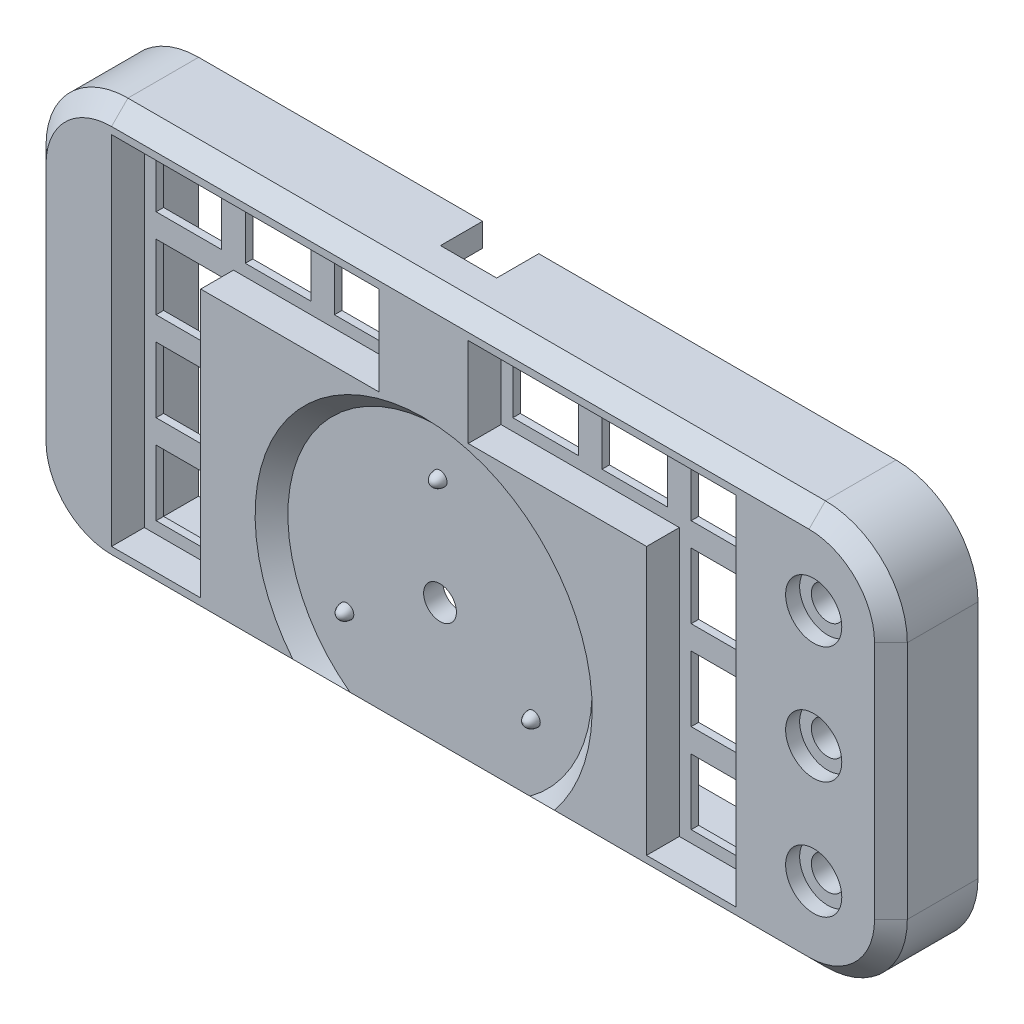
SolidWorks part; units mm, degrees
ref_plane "Alzado" through (0, 0, 0) normal (0, 0, 1) x (1, 0, 0)
ref_plane "Planta" through (0, 0, 0) normal (0, 1, 0) x (1, 0, 0)
ref_plane "Vista lateral" through (0, 0, 0) normal (1, 0, 0) x (0, 0, -1)
sketch "Croquis1" plane through (0, 0, 0) normal (0, 0, 1) x (1, 0, 0)
  line L0 (21.575, 59.675) -> (21.575, 73.675)
  line L1 (0, 0) -> (157.5, 0)
  line L2 (0, 0) -> (0, 76.2)
  line L3 (0, 76.2) -> (157.5, 76.2)
  line L4 (157.5, 0) -> (157.5, 76.2)
  line L5 (2.525, 59.675) -> (16.525, 59.675)
  line L6 (2.525, 59.675) -> (2.525, 73.675)
  line L7 (2.525, 73.675) -> (16.525, 73.675)
  line L8 (16.525, 59.675) -> (16.525, 73.675)
  line L9 (2.525, 59.675) -> (16.525, 73.675) construction
  line L10 (2.525, 73.675) -> (16.525, 59.675) construction
  line L11 (0, 76.2) -> (19.05, 76.2) construction
  line L12 (0, 76.2) -> (0, 57.15) construction
  line L13 (0, 57.15) -> (19.05, 57.15) construction
  line L14 (19.05, 76.2) -> (19.05, 57.15) construction
  line L15 (0, 76.2) -> (19.05, 57.15) construction
  line L16 (0, 57.15) -> (19.05, 76.2) construction
  line L17 (21.575, 59.675) -> (35.575, 59.675)
  line L18 (35.575, 59.675) -> (35.575, 73.675)
  line L19 (21.575, 73.675) -> (35.575, 73.675)
  line L20 (38.1, 76.2) -> (38.1, 57.15) construction
  line L21 (19.05, 57.15) -> (38.1, 57.15) construction
  line L22 (40.625, 59.675) -> (40.625, 73.675)
  line L23 (40.625, 59.675) -> (54.625, 59.675)
  line L24 (54.625, 59.675) -> (54.625, 73.675)
  line L25 (40.625, 73.675) -> (54.625, 73.675)
  line L26 (57.15, 76.2) -> (57.15, 57.15) construction
  line L27 (38.1, 57.15) -> (57.15, 57.15) construction
  line L28 (59.675, 59.675) -> (59.675, 73.675) construction
  line L29 (59.675, 59.675) -> (73.675, 59.675) construction
  line L30 (73.675, 59.675) -> (73.675, 73.675) construction
  line L31 (59.675, 73.675) -> (73.675, 73.675) construction
  line L32 (76.2, 76.2) -> (76.2, 57.15) construction
  line L33 (57.15, 57.15) -> (76.2, 57.15) construction
  line L34 (78.725, 59.675) -> (78.725, 73.675)
  line L35 (78.725, 59.675) -> (92.725, 59.675)
  line L36 (92.725, 59.675) -> (92.725, 73.675)
  line L37 (78.725, 73.675) -> (92.725, 73.675)
  line L38 (95.25, 76.2) -> (95.25, 57.15) construction
  line L39 (76.2, 57.15) -> (95.25, 57.15) construction
  line L40 (97.775, 59.675) -> (97.775, 73.675)
  line L41 (97.775, 59.675) -> (111.775, 59.675)
  line L42 (111.775, 59.675) -> (111.775, 73.675)
  line L43 (97.775, 73.675) -> (111.775, 73.675)
  line L44 (114.3, 76.2) -> (114.3, 57.15) construction
  line L45 (95.25, 57.15) -> (114.3, 57.15) construction
  line L46 (116.825, 59.675) -> (116.825, 73.675)
  line L47 (116.825, 59.675) -> (130.825, 59.675)
  line L48 (130.825, 59.675) -> (130.825, 73.675)
  line L49 (116.825, 73.675) -> (130.825, 73.675)
  line L50 (133.35, 76.2) -> (133.35, 57.15) construction
  line L51 (114.3, 57.15) -> (133.35, 57.15) construction
  line L52 (2.525, 59.675) -> (21.575, 59.675) construction
  line L53 (2.525, 40.625) -> (2.525, 54.625)
  line L54 (2.525, 40.625) -> (16.525, 40.625)
  line L55 (16.525, 40.625) -> (16.525, 54.625)
  line L56 (2.525, 54.625) -> (16.525, 54.625)
  line L57 (0, 38.1) -> (19.05, 38.1) construction
  line L58 (19.05, 57.15) -> (19.05, 38.1) construction
  line L59 (116.825, 40.625) -> (116.825, 54.625)
  line L60 (116.825, 54.625) -> (130.825, 54.625)
  line L61 (130.825, 40.625) -> (130.825, 54.625)
  line L62 (116.825, 40.625) -> (130.825, 40.625)
  line L63 (114.3, 57.15) -> (114.3, 38.1) construction
  line L64 (114.3, 38.1) -> (133.35, 38.1) construction
  line L65 (133.35, 57.15) -> (133.35, 38.1) construction
  line L66 (2.525, 21.575) -> (2.525, 35.575)
  line L67 (2.525, 21.575) -> (16.525, 21.575)
  line L68 (16.525, 21.575) -> (16.525, 35.575)
  line L69 (2.525, 35.575) -> (16.525, 35.575)
  line L70 (0, 19.05) -> (19.05, 19.05) construction
  line L71 (19.05, 38.1) -> (19.05, 19.05) construction
  line L72 (116.825, 21.575) -> (116.825, 35.575)
  line L73 (116.825, 35.575) -> (130.825, 35.575)
  line L74 (130.825, 21.575) -> (130.825, 35.575)
  line L75 (116.825, 21.575) -> (130.825, 21.575)
  line L76 (114.3, 38.1) -> (114.3, 19.05) construction
  line L77 (114.3, 19.05) -> (133.35, 19.05) construction
  line L78 (133.35, 38.1) -> (133.35, 19.05) construction
  line L79 (2.525, 2.525) -> (2.525, 16.525)
  line L80 (2.525, 2.525) -> (16.525, 2.525)
  line L81 (16.525, 2.525) -> (16.525, 16.525)
  line L82 (2.525, 16.525) -> (16.525, 16.525)
  line L83 (0, 0) -> (19.05, 0) construction
  line L84 (19.05, 19.05) -> (19.05, 0) construction
  line L85 (116.825, 2.525) -> (116.825, 16.525)
  line L86 (116.825, 16.525) -> (130.825, 16.525)
  line L87 (130.825, 2.525) -> (130.825, 16.525)
  line L88 (116.825, 2.525) -> (130.825, 2.525)
  line L89 (114.3, 19.05) -> (114.3, 0) construction
  line L90 (114.3, 0) -> (133.35, 0) construction
  line L91 (133.35, 19.05) -> (133.35, 0) construction
  line L92 (2.525, 59.675) -> (2.525, 40.625) construction
  line L104 (133.35, 38.1) -> (150, 38.1) construction
  line L105 (150, 63.1) -> (150, 38.1) construction
  line L121 (150, 38.1) -> (150, 13.1) construction
  line L122 (116.825, 40.625) -> (130.825, 54.625) construction
  circle A0 centre (150, 38.1) radius 3.5
  circle A1 centre (150, 63.1) radius 3.5
  circle A2 centre (150, 13.1) radius 3.5
  circle A3 centre (66.67, 21.2) radius 3.5
  point P5 (9.525, 66.675)
  point P10 (9.525, 66.675)
  point P15 (66.67, 21.2)
  point P119 (98, 28.2)
  dimension "D11" = 7
  dimension "D3" = 19.05
  dimension "D4" = 14
  dimension "D5" = 9.525
  dimension "D6" = 9.525
  dimension "D8" = 19.05
  dimension "D10" = 19.05
  dimension "D13" = 66.67
  dimension "D14" = 76.2
  dimension "D15" = 55
  dimension "D16" = 150
  dimension "D18" = 157.5
  dimension "D19" = 98
  dimension "D20" = 48
  dimension "D22" = 25
  dimension "D17" = 7.5
  dimension "D7" = 7
  dimension "D9" = 4
extrude "Saliente-Extruir1" add sketch "Croquis1" against normal blind 1.6
sketch "Croquis2" plane through (0, 0, 0) normal (0, 0, 1) x (1, 0, 0)
  line L0 (66.67, 21.2) -> (66.67, 83.1935) construction
  line L3 (0, -5) -> (66.67, -5)
  line L4 (166.5, 12.5) -> (166.5, 63.7)
  line L5 (149, 81.2) -> (0, 81.2)
  line L6 (-17.5, 63.7) -> (-17.5, 12.5)
  line L7 (150, 63.1) -> (150, 38.1) construction
  line L8 (0, 76.2) -> (157.5, 76.2) construction
  line L9 (-17.5, 38.1) -> (0, 38.1) construction
  line L10 (0, 0) -> (0, 76.2) construction
  line L11 (66.67, -5) -> (149, -5)
  line L13 (19.05, 0) -> (0, 0)
  line L14 (0, 0) -> (0, 76.2)
  line L15 (0, 76.2) -> (57.15, 76.2)
  line L16 (57.15, 76.2) -> (57.15, 57.15)
  line L17 (57.15, 57.15) -> (19.05, 57.15)
  line L18 (19.05, 57.15) -> (19.05, 0)
  line L19 (19.05, 0) -> (0, 0)
  line L20 (114.3, 0) -> (133.35, 0)
  line L21 (133.35, 0) -> (133.35, 76.2)
  line L22 (133.35, 76.2) -> (76.2, 76.2)
  line L23 (76.2, 76.2) -> (76.2, 57.15)
  line L24 (76.2, 57.15) -> (114.3, 57.15)
  line L25 (114.3, 57.15) -> (114.3, 0)
  arc A0 (166.5, 63.7) -> (149, 81.2) centre (149, 63.7) ccw
  arc A1 (149, -5) -> (166.5, 12.5) centre (149, 12.5) ccw
  arc A2 (0, -5) -> (-17.5, 12.5) centre (0, 12.5) cw
  arc A3 (0, 81.2) -> (-17.5, 63.7) centre (0, 63.7) ccw
  circle A5 centre (150, 13.1) radius 3.5 construction
  circle A6 centre (150, 63.1) radius 3.5 construction
  circle A7 centre (150, 38.1) radius 3.5 construction
  circle A8 centre (150, 13.1) radius 3.5
  circle A9 centre (150, 63.1) radius 3.5
  circle A10 centre (150, 38.1) radius 3.5
  circle A11 centre (66.67, 21.2) radius 3.5 construction
  circle A12 centre (66.67, 21.2) radius 3.5
  dimension "D3" = 17.5
  dimension "D1" = 16.5
  dimension "D2" = 5
extrude "Saliente-Extruir4" add sketch "Croquis2" against normal up to surface (1.6 mm away) and the other way blind 3.5 contours L11 A1 L4 A0 L5 A3 L6 A2 L3 A10 A9 A8 L25 L24 L23 L22 L21 L20 L17 L18 L13 L14 L15 L16 region at (76.8141, 34.4181, 0) up to face at (153.5, 13.1, -1.6)
sketch "Croquis3" plane through (0, 0, 3.5) normal (0, 0, 1) x (1, 0, 0)
  line L0 (76.2, 57.15) -> (114.3, 57.15) construction
  line L1 (76.2, 76.2) -> (76.2, 57.15) construction
  line L2 (133.35, 76.2) -> (76.2, 76.2) construction
  line L3 (133.35, 0) -> (133.35, 76.2) construction
  line L4 (114.3, 57.15) -> (114.3, 0) construction
  line L5 (114.3, 0) -> (133.35, 0) construction
  line L6 (19.05, 0) -> (0, 0) construction
  line L7 (19.05, 57.15) -> (19.05, 0) construction
  line L8 (57.15, 57.15) -> (19.05, 57.15) construction
  line L9 (57.15, 76.2) -> (57.15, 57.15) construction
  line L10 (0, 76.2) -> (57.15, 76.2) construction
  line L11 (0, 76.2) -> (0, 0) construction
  line L12 (76.2, 57.15) -> (114.3, 57.15)
  line L13 (76.2, 76.2) -> (76.2, 57.15)
  line L14 (133.35, 76.2) -> (76.2, 76.2)
  line L15 (133.35, 0) -> (133.35, 76.2)
  line L16 (114.3, 57.15) -> (114.3, 0)
  line L17 (114.3, 0) -> (133.35, 0)
  line L18 (19.05, 0) -> (0, 0)
  line L19 (19.05, 57.15) -> (19.05, 0)
  line L20 (57.15, 57.15) -> (19.05, 57.15)
  line L21 (57.15, 76.2) -> (57.15, 57.15)
  line L22 (0, 76.2) -> (57.15, 76.2)
  line L23 (0, 76.2) -> (0, 0)
  line L24 (85.9004, -5) -> (149, -5)
  line L28 (149, 81.2) -> (0, 81.2)
  line L29 (-17.5, 63.7) -> (-17.5, 12.5)
  line L30 (0, -5) -> (149, -5)
  line L31 (166.5, 12.5) -> (166.5, 63.7)
  line L32 (149, 81.2) -> (0, 81.2)
  line L33 (-17.5, 63.7) -> (-17.5, 12.5)
  line L34 (0, -5) -> (47.4396, -5)
  line L35 (166.5, 12.5) -> (166.5, 63.7)
  circle A0 centre (150, 63.1) radius 3.5 construction
  circle A1 centre (150, 38.1) radius 3.5 construction
  circle A2 centre (150, 13.1) radius 3.5 construction
  circle A3 centre (66.67, 21.2) radius 3.5 construction
  circle A4 centre (150, 63.1) radius 3.5
  circle A5 centre (150, 38.1) radius 3.5
  circle A6 centre (150, 13.1) radius 3.5
  circle A7 centre (66.67, 21.2) radius 3.5 construction
  arc A8 (85.9004, -5) -> (47.4396, -5) centre (66.67, 21.2) ccw
  arc A12 (0, 81.2) -> (-17.5, 63.7) centre (0, 63.7) ccw
  arc A13 (-17.5, 12.5) -> (0, -5) centre (0, 12.5) ccw
  arc A14 (149, -5) -> (166.5, 12.5) centre (149, 12.5) ccw
  arc A15 (166.5, 63.7) -> (149, 81.2) centre (149, 63.7) ccw
  arc A16 (0, 81.2) -> (-17.5, 63.7) centre (0, 63.7) ccw
  arc A17 (-17.5, 12.5) -> (0, -5) centre (0, 12.5) ccw
  arc A18 (149, -5) -> (166.5, 12.5) centre (149, 12.5) ccw
  arc A19 (166.5, 63.7) -> (149, 81.2) centre (149, 63.7) ccw
  dimension "D2" = 65
  dimension "D1" = 0
extrude "Saliente-Extruir5" add sketch "Croquis3" along normal blind 3.5
chamfer "Chaflán1" distance 3.5 angle 45 10 edges at (117.4502, -5, 7) (161.3744, 0.1256, 7) (166.5, 38.1, 7) (161.3744, 76.0744, 7) (74.5, 81.2, 7) (-12.3744, 76.0744, 7) (-17.5, 38.1, 7) (-12.3744, 0.1256, 7) (23.7198, -5, 7) (66.67, 53.7, 7)
sketch "Croquis4" plane through (0, 0, -1.6) normal (0, 0, -1) x (-1, 0, 0)
  line L1 (-157.25, 55.85) -> (-142.75, 55.85)
  line L2 (-157.25, 55.85) -> (-157.25, 70.35)
  line L3 (-157.25, 70.35) -> (-142.75, 70.35)
  line L4 (-142.75, 55.85) -> (-142.75, 70.35)
  line L5 (-157.25, 55.85) -> (-142.75, 70.35) construction
  line L6 (-157.25, 70.35) -> (-142.75, 55.85) construction
  line L7 (-157.25, 30.85) -> (-142.75, 30.85)
  line L8 (-157.25, 30.85) -> (-157.25, 45.35)
  line L9 (-157.25, 45.35) -> (-142.75, 45.35)
  line L10 (-142.75, 30.85) -> (-142.75, 45.35)
  line L11 (-157.25, 30.85) -> (-142.75, 45.35) construction
  line L12 (-157.25, 45.35) -> (-142.75, 30.85) construction
  line L13 (-157.25, 5.85) -> (-142.75, 5.85)
  line L14 (-157.25, 5.85) -> (-157.25, 20.35)
  line L15 (-157.25, 20.35) -> (-142.75, 20.35)
  line L16 (-142.75, 5.85) -> (-142.75, 20.35)
  line L17 (-157.25, 5.85) -> (-142.75, 20.35) construction
  line L18 (-157.25, 20.35) -> (-142.75, 5.85) construction
  line L19 (-73.92, 13.95) -> (-59.42, 13.95)
  line L20 (-73.92, 13.95) -> (-73.92, 28.45)
  line L21 (-73.92, 28.45) -> (-59.42, 28.45)
  line L22 (-59.42, 13.95) -> (-59.42, 28.45)
  line L23 (-73.92, 13.95) -> (-59.42, 28.45) construction
  line L24 (-73.92, 28.45) -> (-59.42, 13.95) construction
  point P0 (-150, 63.1)
  point P6 (-150, 38.1)
  point P12 (-150, 13.1)
  point P18 (-66.67, 21.2)
  dimension "D1" = 14.5
extrude "Cortar-Extruir1" cut sketch "Croquis4" against normal blind 1
sketch "Croquis5" plane through (0, 0, -1.6) normal (0, 0, -1) x (-1, 0, 0)
  line L0 (0, 76.2) -> (-149, 76.2)
  line L1 (-161.5, 63.7) -> (-161.5, 12.5)
  line L2 (-149, 0) -> (0, 0) construction
  line L4 (0, 81.2) -> (-149, 81.2)
  line L5 (-166.5, 63.7) -> (-166.5, 12.5)
  line L6 (-149, -5) -> (0, -5)
  line L7 (17.5, 12.5) -> (17.5, 63.7)
  line L8 (0, 81.2) -> (-149, 81.2)
  line L9 (-166.5, 63.7) -> (-166.5, 12.5)
  line L10 (-149, -5) -> (0, -5)
  line L11 (17.5, 12.5) -> (17.5, 63.7)
  line L12 (0, 0) -> (0, 76.2)
  line L13 (-149, 0) -> (0, 0)
  line L14 (0, 76.2) -> (-149, 76.2) construction
  line L16 (12.5, 12.5) -> (12.5, 63.7) construction
  arc A0 (-149, 76.2) -> (-161.5, 63.7) centre (-149, 63.7) ccw
  arc A1 (-161.5, 12.5) -> (-149, 0) centre (-149, 12.5) ccw
  arc A4 (-149, 81.2) -> (-166.5, 63.7) centre (-149, 63.7) ccw
  arc A5 (-166.5, 12.5) -> (-149, -5) centre (-149, 12.5) ccw
  arc A6 (0, -5) -> (17.5, 12.5) centre (0, 12.5) ccw
  arc A7 (17.5, 63.7) -> (0, 81.2) centre (0, 63.7) ccw
  arc A8 (-149, 81.2) -> (-166.5, 63.7) centre (-149, 63.7) ccw
  arc A9 (-166.5, 12.5) -> (-149, -5) centre (-149, 12.5) ccw
  arc A10 (0, -5) -> (17.5, 12.5) centre (0, 12.5) ccw
  arc A11 (17.5, 63.7) -> (0, 81.2) centre (0, 63.7) ccw
  arc A16 (12.5, 63.7) -> (0, 76.2) centre (0, 63.7) ccw construction
  arc A17 (0, 0) -> (12.5, 12.5) centre (0, 12.5) ccw construction
  dimension "D1" = 0
  dimension "D2" = 5
extrude "Saliente-Extruir6" add sketch "Croquis5" along normal blind 10
sketch "Croquis7" plane through (0, 0, -1.6) normal (0, 0, -1) x (-1, 0, 0)
  line L0 (-150, 45.35) -> (-150, 55.85) construction
  line L1 (-142.75, 45.35) -> (-157.25, 45.35) construction
  line L2 (-157.25, 55.85) -> (-142.75, 55.85) construction
  line L3 (-150, 20.35) -> (-150, 30.85) construction
  line L4 (-142.75, 20.35) -> (-157.25, 20.35) construction
  line L5 (-157.25, 30.85) -> (-142.75, 30.85) construction
  line L6 (-150, 25.6) -> (-161.5, 25.6) construction
  line L7 (-161.5, 63.7) -> (-161.5, 12.5) construction
  line L8 (-150, 50.6) -> (-161.5, 50.6) construction
  line L9 (0, 76.2) -> (-149, 76.2) construction
  line L10 (-75.92, 76.2) -> (-57.42, 76.2) construction
  line L11 (-75.92, 76.2) -> (-75.92, 45.2) construction
  line L12 (-75.92, 45.2) -> (-57.42, 45.2) construction
  line L13 (-57.42, 76.2) -> (-57.42, 45.2) construction
  line L14 (-66.67, 45.2) -> (-66.67, 21.2) construction
  circle A0 centre (-161.5, 25.6) radius 4
  circle A1 centre (-161.5, 50.6) radius 4
  circle A2 centre (-50, 35) radius 4
  circle A4 centre (-85, 8) radius 4
  dimension "D3" = 8
  dimension "D1" = 31
  dimension "D2" = 18.5
  dimension "D4" = 35
  dimension "D5" = 8
  dimension "D6" = 50
  dimension "D7" = 85
extrude "Saliente-Extruir7" add sketch "Croquis7" along normal up to surface (10 mm away) up to face at (74.5, 38.1, -11.6)
sketch "Croquis8" plane through (0, 0, -11.6) normal (0, 0, -1) x (-1, 0, 0)
  line L0 (7.5, 68.1) -> (7.5, 8.1) construction
  line L1 (7.5, 38.1) -> (17.5, 38.1) construction
  line L2 (17.5, 12.5) -> (17.5, 63.7) construction
  circle A0 centre (-161.5, 50.6) radius 2
  circle A1 centre (-161.5, 25.6) radius 2
  circle A2 centre (-85, 8) radius 2
  circle A3 centre (-50, 35) radius 2
  circle A6 centre (7.5, 8.1) radius 2
  circle A7 centre (7.5, 68.1) radius 2
  dimension "D1" = 4
  dimension "D2" = 60
  dimension "D3" = 10
extrude "Cortar-Extruir2" cut sketch "Croquis8" against normal blind 5
sketch "Croquis9" plane through (0, 0, -1.6) normal (0, 0, -1) x (-1, 0, 0)
  line L0 (-66.67, 21.2) -> (-66.67, 76.2) construction
  line L1 (0, 76.2) -> (-149, 76.2) construction
  line L8 (-56.67, 44.2) -> (-76.67, 44.2)
  line L9 (-56.67, 44.2) -> (-56.67, 76.2)
  line L16 (-56.67, 76.2) -> (-76.67, 76.2)
  line L17 (-76.67, 44.2) -> (-76.67, 76.2)
  line L18 (-56.67, 44.2) -> (-76.67, 76.2) construction
  line L19 (-56.67, 76.2) -> (-76.67, 44.2) construction
  point P5 (-66.67, 60.2)
  dimension "D1" = 20
  dimension "D2" = 32
extrude "Saliente-Extruir8" add sketch "Croquis9" along normal up to surface (10 mm away) up to face at (-9.5, 68.1, -11.6)
sketch "Croquis10" plane through (0, 44.2, 0) normal (0, -1, 0) x (1, 0, 0)
  line L0 (66.67, -11.6) -> (66.67, -1.6) construction
  line L1 (76.67, -11.6) -> (56.67, -11.6) construction
  line L2 (76.67, -1.6) -> (56.67, -1.6) construction
  line L3 (76.67, -1.6) -> (76.67, -3.2) construction
  line L4 (76.67, -11.6) -> (76.67, -1.6) construction
  line L5 (76.67, -3.2) -> (76.67, -4.8) construction
  line L6 (76.67, -3.2) -> (56.67, -3.2) construction
  line L7 (56.67, -11.6) -> (56.67, -1.6) construction
  line L8 (75.92, -3.2) -> (57.42, -3.2)
  line L9 (75.92, -3.2) -> (75.92, -5.45)
  line L10 (75.92, -5.45) -> (75.67, -5.45)
  line L11 (75.67, -5.45) -> (74.92, -7.45)
  line L12 (74.92, -7.45) -> (76.67, -7.45)
  line L13 (76.67, -7.45) -> (76.67, -11.6)
  line L14 (76.67, -11.6) -> (56.67, -11.6)
  line L15 (75.92, -5.45) -> (75.92, -7.45) construction
  line L16 (56.67, -7.45) -> (56.67, -11.6)
  line L17 (58.42, -7.45) -> (56.67, -7.45)
  line L18 (57.67, -5.45) -> (58.42, -7.45)
  line L19 (57.42, -5.45) -> (57.67, -5.45)
  line L20 (57.42, -3.2) -> (57.42, -5.45)
  point P18 (66.67, -3.2)
  dimension "D1" = 1.6
  dimension "D2" = 1.6
  dimension "D3" = 18.5
  dimension "D4" = 2.25
  dimension "D5" = 1
  dimension "D6" = 2
  dimension "D7" = 0.25
extrude "Cortar-Extruir4" cut sketch "Croquis10" against normal up to surface (32 mm away) up to face at (112.835, 76.2, -6.6)
sketch "Croquis14" plane through (0, 44.2, 0) normal (0, -1, 0) x (1, 0, 0)
  line L0 (56.67, -7.45) -> (56.67, -1.6) construction
  line L1 (76.67, -7.45) -> (56.67, -7.45)
  line L2 (76.67, -7.45) -> (76.67, -3.2)
  line L3 (76.67, -3.2) -> (56.67, -3.2)
  line L4 (56.67, -7.45) -> (56.67, -3.2)
  line L5 (75.92, -3.2) -> (57.42, -3.2) construction
extrude "Cortar-Extruir8" cut sketch "Croquis14" against normal blind 22
sketch "Croquis11" plane through (0, 76.2, 0) normal (0, -1, 0) x (1, 0, 0)
  line L1 (0, -11.6) -> (149, -11.6) construction
  line L2 (0, -11.6) -> (149, -11.6) construction
  line L11 (0, -6.6) -> (149, -6.6) construction
  line L12 (0, -11.6) -> (0, -1.6) construction
  line L13 (149, -11.6) -> (149, -1.6) construction
  line L14 (66.67, -3.2) -> (66.67, -11.6) construction
  line L15 (57.42, -3.2) -> (75.92, -3.2) construction
  line L16 (60.67, -10.6) -> (60.67, -11.6)
  line L17 (60.67, -10.6) -> (72.67, -10.6) construction
  line L18 (60.67, -10.6) -> (60.67, -2.6)
  line L19 (60.67, -2.6) -> (72.67, -2.6)
  line L20 (72.67, -10.6) -> (72.67, -2.6)
  line L21 (60.67, -10.6) -> (72.67, -2.6) construction
  line L22 (60.67, -2.6) -> (72.67, -10.6) construction
  line L23 (60.67, -11.6) -> (72.67, -11.6)
  line L24 (72.67, -11.6) -> (72.67, -10.6)
  point P12 (66.67, -6.6)
  dimension "D1" = 5
  dimension "D2" = 12
  dimension "D3" = 8
extrude "Cortar-Extruir5" cut sketch "Croquis11" against normal through all
sketch "Croquis15" plane through (0, 0, 3.5) normal (0, 0, 1) x (1, 0, 0)
  line L0 (66.67, 21.2) -> (66.67, 44.2) construction
  circle A0 centre (66.67, 21.2) radius 23 construction
  dimension "D1" = 46
ref_plane "Plano1" through (66.67, 0, 0) normal (-1, 0, 0) x (0, 0, 1)
sketch "Croquis16" plane through (66.67, 0, 0) normal (-1, 0, 0) x (0, 0, 1)
  line L0 (3.5, 21.2) -> (3.5, 44.2) construction
  line L1 (3.5, 45.7) -> (3.5, 42.7)
  line L2 (3.5, 44.2) -> (5.5, 44.2) construction
  ellipse E0 centre (3.5, 44.2) end of major axis (1.5, 44.2) minor radius 1.5 (3.5, 42.7) -> (3.5, 45.7) ccw
  dimension "D1" = 3
  dimension "D2" = 2
revolve "Revolución1" add sketch "Croquis16" angle 360 about L2 region at (66.67, 44.8366, 4.3488)
pattern_circular "MatrizC1" count 3 over 360 about axis through (66.67, 21.2, -1.6) along (0, 0, 1) of "Revolución1"
sketch "Croquis17" plane through (0, 0, -0.6) normal (0, 0, -1) x (-1, 0, 0)
  line L0 (-157.25, 63.1) -> (-150, 63.1) construction
  line L1 (-157.25, 70.35) -> (-157.25, 55.85) construction
  line L2 (-157.25, 38.1) -> (-150, 38.1) construction
  line L3 (-157.25, 45.35) -> (-157.25, 30.85) construction
  line L4 (-157.25, 13.1) -> (-150, 13.1) construction
  line L5 (-157.25, 20.35) -> (-157.25, 5.85) construction
  line L6 (-73.92, 21.2) -> (-66.67, 21.2) construction
  line L7 (-73.92, 28.45) -> (-73.92, 13.95) construction
  line L9 (-157, 64.1) -> (-155.5, 64.1)
  line L10 (-157, 64.1) -> (-157, 62.1)
  line L11 (-157, 62.1) -> (-155.5, 62.1)
  line L12 (-155.5, 64.1) -> (-155.5, 62.1)
  line L13 (-157, 64.1) -> (-155.5, 62.1) construction
  line L14 (-157, 62.1) -> (-155.5, 64.1) construction
  line L15 (-157, 37.1) -> (-155.5, 37.1)
  line L16 (-157, 37.1) -> (-157, 39.1)
  line L17 (-157, 39.1) -> (-155.5, 39.1)
  line L18 (-155.5, 37.1) -> (-155.5, 39.1)
  line L19 (-157, 37.1) -> (-155.5, 39.1) construction
  line L20 (-157, 39.1) -> (-155.5, 37.1) construction
  line L21 (-155.5, 12.1) -> (-157, 12.1)
  line L22 (-155.5, 12.1) -> (-155.5, 14.1)
  line L23 (-155.5, 14.1) -> (-157, 14.1)
  line L24 (-157, 12.1) -> (-157, 14.1)
  line L25 (-155.5, 12.1) -> (-157, 14.1) construction
  line L26 (-155.5, 14.1) -> (-157, 12.1) construction
  line L27 (-73.67, 20.2) -> (-72.17, 20.2)
  line L28 (-73.67, 20.2) -> (-73.67, 22.2)
  line L29 (-73.67, 22.2) -> (-72.17, 22.2)
  line L30 (-72.17, 20.2) -> (-72.17, 22.2)
  line L31 (-73.67, 20.2) -> (-72.17, 22.2) construction
  line L32 (-73.67, 22.2) -> (-72.17, 20.2) construction
  point P20 (-156.25, 63.1)
  point P25 (-156.25, 38.1)
  point P30 (-156.25, 13.1)
  point P35 (-72.92, 21.2)
  dimension "D1" = 7
  dimension "D2" = 1.5
  dimension "D3" = 2
  dimension "D4" = 7
extrude "Cortar-Extruir9" cut sketch "Croquis17" against normal blind 2
sketch "Croquis18" plane through (0, 0, 7) normal (0, 0, 1) x (1, 0, 0)
  circle A0 centre (150, 63.1) radius 6
  circle A1 centre (150, 38.1) radius 6
  circle A2 centre (150, 13.1) radius 6
  dimension "D1" = 12
extrude "Cortar-Extruir10" cut sketch "Croquis18" against normal blind 3
